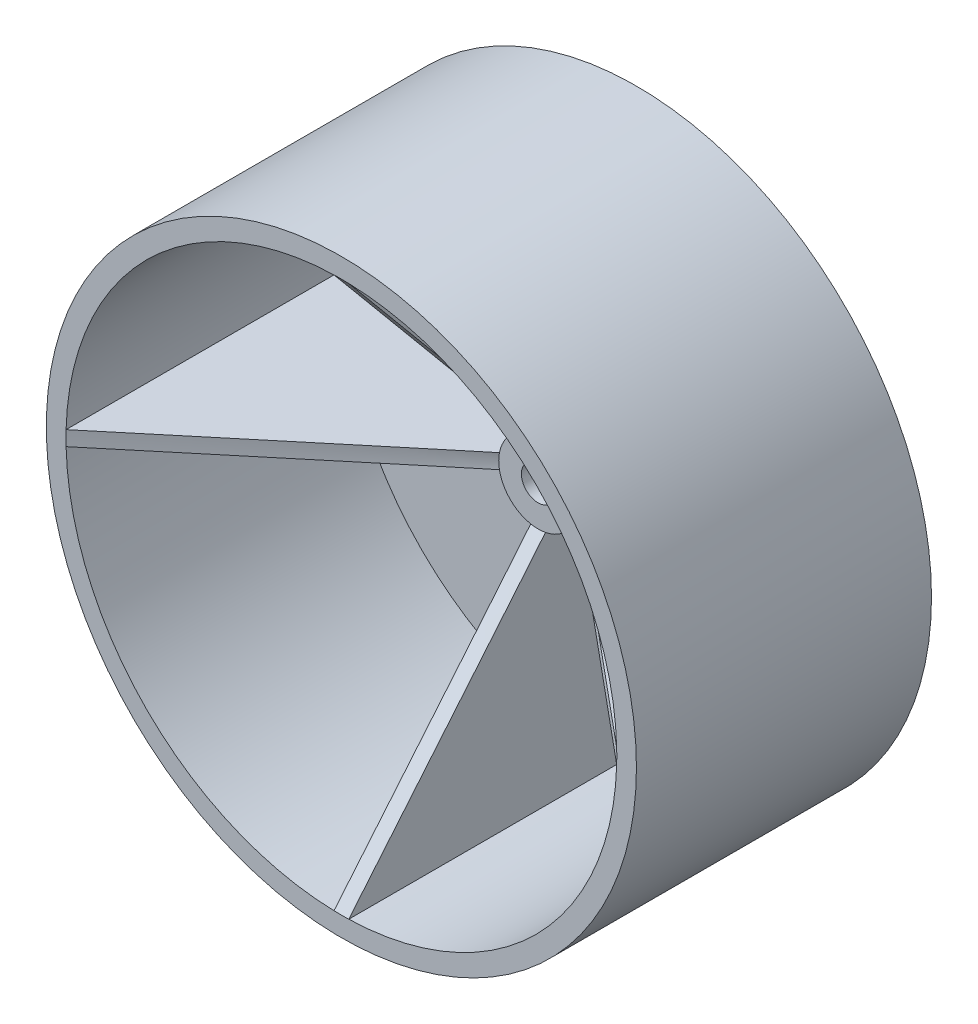
SolidWorks part; units mm, degrees
ref_plane "Front Plane" through (0, 0, 0) normal (0, 0, 1) x (1, 0, 0)
ref_plane "Top Plane" through (0, 0, 0) normal (0, 1, 0) x (1, 0, 0)
ref_plane "Right Plane" through (0, 0, 0) normal (1, 0, 0) x (0, 0, -1)
sketch "Sketch1" plane through (0, 0, 0) normal (0, 0, 1) x (1, 0, 0)
  line L0 (-1.25, 1.1522) -> (1.25, 1.1522)
  line L1 (-0.75, 3.9291) -> (-0.75, 27.99)
  line L2 (0.75, 3.9291) -> (0.75, 27.99)
  line L3 (0, -55) -> (0, 55) construction
  circle A0 centre (0, 0) radius 30
  arc A1 (-1.25, 1.1522) -> (1.25, 1.1522) centre (0, 0) ccw
  circle A2 centre (0, 0) radius 28
  circle A3 centre (0, 0) radius 4
  dimension "D1" = 60
  dimension "D3" = 2.5
  dimension "D4" = 2
  dimension "D5" = 8
  dimension "D2" = 1.7
  dimension "D6" = 1.5
  dimension "D7" = 0.75
extrude "Boss-Extrude1" add sketch "Sketch1" against normal blind 2 contours A3 L2 A2 L1 | A0 A2 | A3 L1 A2 L2 | A3 A1 L0 region at (-3.0542, -3.6924, 0) region at (0, 15.9865, 0) region at (0, 3.8869, 0) region at (-29.1515, 0, 0)
extrude "Boss-Extrude2" add sketch "Sketch1<3>" along normal blind 8 contours A3 A1 L0 region at (0, 3.8869, 0)
sketch "Sketch1<3>" plane through (0, 0, 0) normal (0, 0, 1) x (1, 0, 0) same geometry as "Sketch1"
extrude "Boss-Extrude3" add sketch "Sketch1<4>" along normal blind 28 contours A3 L2 A2 L1 | A0 A2 region at (0, 15.9865, 0) region at (-29.1515, 0, 0)
sketch "Sketch1<4>" plane through (0, 0, 0) normal (0, 0, 1) x (1, 0, 0) same geometry as "Sketch1"
chamfer "Chamfer1" distance 24 distance2 20 1 edges at (0, 4, 28) first distance on face at (0, 1.9798, 28)
pattern_circular "CirPattern1" count 4 over 360 about axis through (0, 0, 28) along (0, 0, 1) of "Boss-Extrude3", "Chamfer1"
